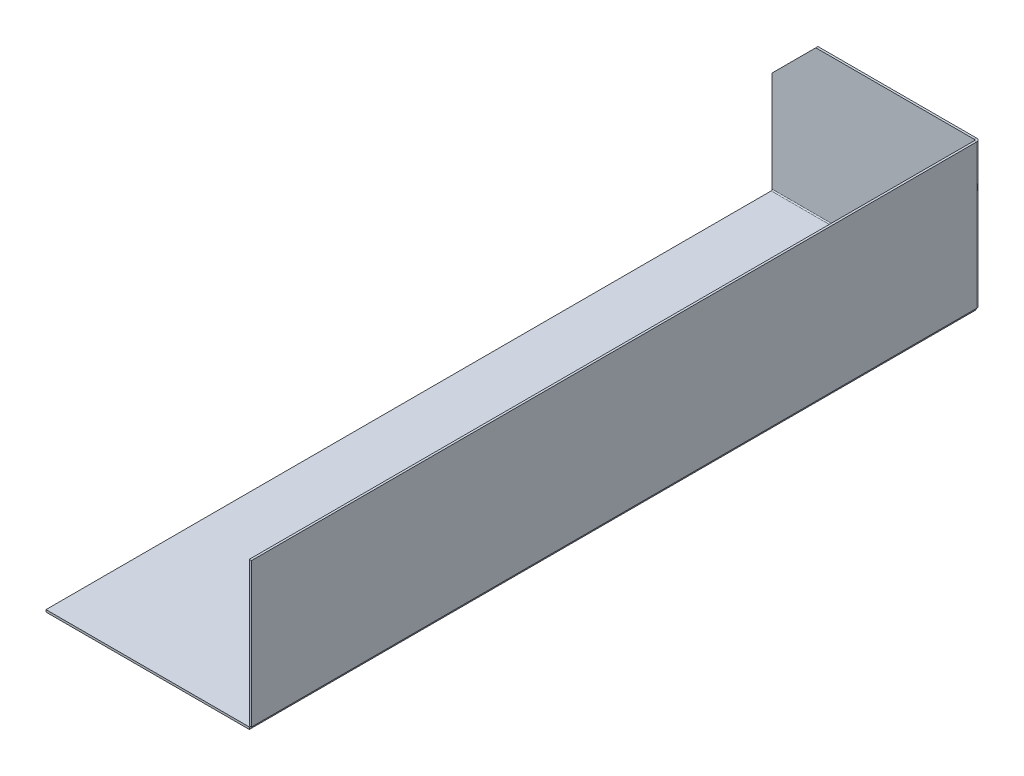
SolidWorks part; units mm, degrees
note: The reader was unsure of these and kept them because the rebuilt part matched: flange length of "Kenar-Flanş5", "Kenar-Flanş6".
ref_plane "Ön Düzlem" through (0, 0, 0) normal (0, 0, 1) x (1, 0, 0)
ref_plane "Üst Düzlem" through (0, 0, 0) normal (0, 1, 0) x (1, 0, 0)
ref_plane "Sağ Düzlem" through (0, 0, 0) normal (1, 0, 0) x (0, 0, -1)
sketch "Çizim1" plane through (0, 0, 0) normal (0, 0, 1) x (1, 0, 0)
  line L0 (0, 0) -> (0, 70)
  line L1 (140, 100) -> (30, 100)
  line L2 (140, 100) -> (140, 0)
  line L3 (140, 0) -> (0, 0)
  line L4 (0, 70) -> (30, 100)
  point P1 (0, 100)
  dimension "D1" = 140
  dimension "D2" = 100
base flange "Taban-Flanş2" sketch "Çizim1" thickness 1.5 reverse thickness direction no parameters "D1"=0.7366
edge flange "Kenar-Flanş5" sketch "Çizim43" flange angle 90 flange length 500 flange position material outside bend radius 0.7366 thickness 1.5 relief rectangular parameters "D6"=10
sketch "Çizim43" plane through (0, 0, 0) normal (0, 1, 0) x (-1, 0, 0)
  line L2 (-140, 0) -> (-140, 500)
  line L3 (-140, 500) -> (0, 500)
  line L4 (0, 500) -> (0, 0)
  line L6 (0, 0) -> (-140, 0) construction
  line L7 (0, 0) -> (-140, 0)
bend "KenarBükümü9" bend radius 0.7366 bend angle 90 parameters "D5"=1
edge flange "Kenar-Flanş6" sketch "Çizim46" flange angle 90 flange length 500 flange position material outside bend radius 0.7366 thickness 1.5 relief none parameters "D6"=10
sketch "Çizim46" plane through (140, 0, 0) normal (-1, 0, 0) x (0, -1, 0)
  line L1 (-0.7366, 0) -> (-100, 0) construction
  line L2 (-100, 0) -> (-100, 500)
  line L3 (-100, 500) -> (-0.7366, 500)
  line L4 (-0.7366, 500) -> (-0.7366, 0)
  line L5 (-0.7366, 0) -> (-100, 0)
bend "KenarBükümü10" bend radius 0.7366 bend angle 90 parameters "D5"=2
sketch "Büküm-Çizgileri3" [suppressed] plane through (0, 0, 0) normal (0, 1, 0) x (1, 0, 0)
sketch "Sınırlandırma-Kutusu3" [suppressed] plane through (0, 0, 0) normal (0, 1, 0) x (1, 0, 0)
sheet metal parameters "Sac-Levha4" thickness 1.5 parameters "D1"=0.7366
flat pattern "Düz-Çoğaltma4" [suppressed]
sketch "Büküm-Çizgileri4" plane through (0, 0, 0) normal (0, 1, 0) x (1, 0, 0)
sketch3d "Sınırlandırma-Kutusu4" [suppressed]
  line L0 (0, 0, 0) -> (140, 0, 0) construction
  line L1 (0, 100, 0) -> (140, 100, 0) construction
  line L2 (0, 0, 0) -> (0, 100, 0) construction
  line L3 (140, 0, 0) -> (140, 100, 0) construction
sheet metal parameters "Sac-Levha9" thickness 1.5 parameters "D1"=0.7366
flat pattern "Düz-Çoğaltma4"
sketch "Büküm-Çizgileri4" plane through (0, 0, 0) normal (0, 0, 1) x (1, 0, 0)
  line L0 (0, -0.431) -> (140, -0.431) construction
  line L1 (0, -0.431) -> (140, -0.431) construction
sketch3d "Sınırlandırma-Kutusu4" [suppressed]
  line L0 (140, 100, 0) -> (140, -500.8619, 0) construction
  line L1 (0, 100, 0) -> (0, -500.8619, 0) construction
  line L2 (140, 100, 0) -> (0, 100, 0) construction
  line L3 (140, -500.8619, 0) -> (0, -500.8619, 0) construction
bend of the flat pattern "Düzleştirme TipiKenarBükümü9>1"
sheet metal parameters "Sac-Levha10" thickness 1.5 parameters "D1"=0.7366
flat pattern "Düz-Çoğaltma4"
sketch "Büküm-Çizgileri4" plane through (0, 0, 0) normal (0, 0, 1) x (1, 0, 0)
  line L0 (0, -0.431) -> (140, -0.431) construction
  line L1 (0, -0.431) -> (140, -0.431) construction
  line L2 (140.431, 0.7366) -> (140.431, 100) construction
  line L3 (140.431, 0.7366) -> (140.431, 100) construction
sketch3d "Sınırlandırma-Kutusu4" [suppressed]
  line L0 (0, -500.8619, 0) -> (640.8619, -500.8619, 0) construction
  line L1 (0, 100, 0) -> (640.8619, 100, 0) construction
  line L2 (0, -500.8619, 0) -> (0, 100, 0) construction
  line L3 (640.8619, -500.8619, 0) -> (640.8619, 100, 0) construction
bend of the flat pattern "Düzleştirme TipiKenarBükümü9>1"
bend of the flat pattern "Düzleştirme TipiKenarBükümü10>1"
